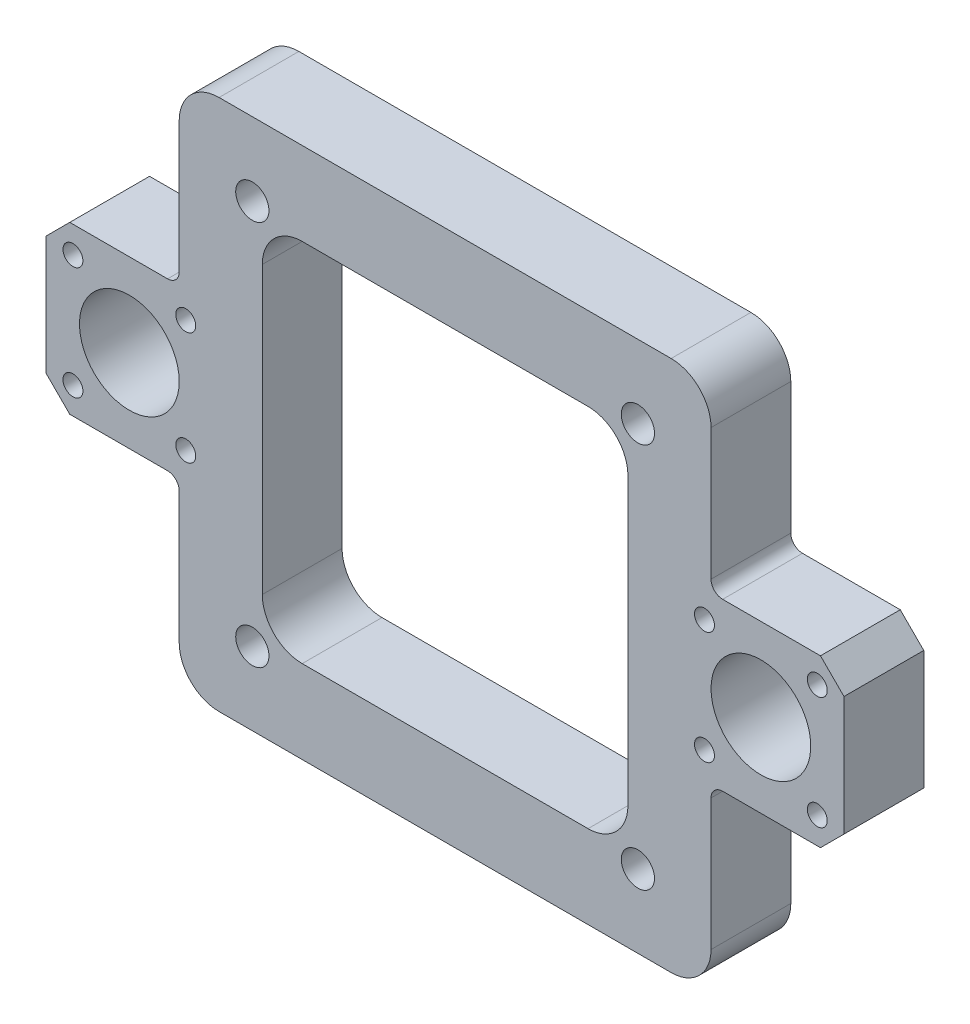
SolidWorks part; units mm, degrees
ref_plane "Front Plane" through (0, 0, 0) normal (0, 0, 1) x (1, 0, 0)
ref_plane "Top Plane" through (0, 0, 0) normal (0, 1, 0) x (1, 0, 0)
ref_plane "Right Plane" through (0, 0, 0) normal (1, 0, 0) x (0, 0, -1)
sketch "Sketch1" plane through (0, 0, 0) normal (0, 0, 1) x (1, 0, 0)
  line L0 (-47.5, 0) -> (47.5, 0) construction
  line L1 (0, 0) -> (0, 17.3262) construction
  line L2 (-56.4645, 12.5) -> (-41.75, 12.5)
  line L3 (-40, 14.25) -> (-40, 34)
  line L12 (-56.4645, 12.5) -> (-60, 8.9645)
  line L13 (-60, 8.9645) -> (-60, -8.9645)
  line L14 (34, 40) -> (-34, 40)
  line L15 (60, 8.9645) -> (60, -8.9645)
  line L16 (56.4645, 12.5) -> (60, 8.9645)
  line L17 (56.4645, 12.5) -> (41.75, 12.5)
  line L18 (40, 14.25) -> (40, 34)
  line L19 (-56.4645, -12.5) -> (-60, -8.9645)
  line L20 (-56.4645, -12.5) -> (-41.75, -12.5)
  line L21 (-40, -14.25) -> (-40, -34)
  line L22 (34, -40) -> (-34, -40)
  line L23 (40, -14.25) -> (40, -34)
  line L24 (56.4645, -12.5) -> (41.75, -12.5)
  line L25 (56.4645, -12.5) -> (60, -8.9645)
  line L26 (-55.9853, 8.4853) -> (-39.0147, -8.4853) construction
  line L27 (-55.9853, -8.4853) -> (-39.0147, 8.4853) construction
  circle A0 centre (-47.5, 0) radius 7.5
  arc A12 (-41.75, 12.5) -> (-40, 14.25) centre (-41.75, 14.25) ccw
  arc A13 (-40, 34) -> (-34, 40) centre (-34, 34) cw
  arc A14 (41.75, 12.5) -> (40, 14.25) centre (41.75, 14.25) cw
  arc A15 (40, 34) -> (34, 40) centre (34, 34) ccw
  arc A16 (-41.75, -12.5) -> (-40, -14.25) centre (-41.75, -14.25) cw
  arc A17 (-40, -34) -> (-34, -40) centre (-34, -34) ccw
  arc A18 (40, -34) -> (34, -40) centre (34, -34) cw
  arc A19 (41.75, -12.5) -> (40, -14.25) centre (41.75, -14.25) ccw
  circle A20 centre (47.5, 0) radius 7.5
  circle A21 centre (-55.9853, 8.4853) radius 1.5
  circle A22 centre (-39.0147, -8.4853) radius 1.5
  circle A23 centre (-39.0147, 8.4853) radius 1.5
  circle A24 centre (-55.9853, -8.4853) radius 1.5
  circle A25 centre (39.0147, -8.4853) radius 1.5
  circle A26 centre (55.9853, -8.4853) radius 1.5
  circle A27 centre (55.9853, 8.4853) radius 1.5
  circle A28 centre (39.0147, 8.4853) radius 1.5
  circle A29 centre (-29, 29) radius 2.5
  circle A33 centre (29, 29) radius 2.5
  circle A34 centre (29, -29) radius 2.5
  circle A35 centre (-29, -29) radius 2.5
  point P28 (0, 40)
  point P29 (-60, 0)
  point P44 (60, 0)
  point P65 (-34, 24)
  point P66 (0, 0)
  point P67 (0, 0)
  point P68 (-34, -34)
  point P70 (-29.5254, 29.7048)
  dimension "D2" = 15
  dimension "D3" = 25
  dimension "D6" = 1.75
  dimension "D11" = 3
  dimension "D13" = 6
  dimension "D15" = 5
  dimension "D1" = 95
  dimension "D4" = 120
  dimension "D5" = 40
  dimension "D7" = 135
  dimension "D8" = 80
  dimension "D9" = 5
  dimension "D10" = 24
  dimension "D12" = 135
  dimension "D14" = 58
  dimension "D16" = 58
extrude "Boss-Extrude1" add sketch "Sketch1" along normal blind 12
sketch "Sketch2" plane through (0, 0, 12) normal (0, 0, 1) x (1, 0, 0)
  line L0 (-21.5, 21.5) -> (21.5, -21.5) construction
  line L1 (-21.5, 27.5) -> (21.5, 27.5)
  line L2 (-27.5, 21.5) -> (-27.5, -21.5)
  line L3 (-21.5, -27.5) -> (21.5, -27.5)
  line L4 (27.5, 21.5) -> (27.5, -21.5)
  arc A0 (-27.5, -21.5) -> (-21.5, -27.5) centre (-21.5, -21.5) ccw
  arc A1 (21.5, -27.5) -> (27.5, -21.5) centre (21.5, -21.5) ccw
  arc A2 (27.5, 21.5) -> (21.5, 27.5) centre (21.5, 21.5) ccw
  arc A3 (-21.5, 27.5) -> (-27.5, 21.5) centre (-21.5, 21.5) ccw
  point P12 (-21.6808, 21.6808)
  dimension "D1" = 6
  dimension "D2" = 55
extrude "Cut-Extrude1" cut sketch "Sketch2" against normal through all both and the other way through all
